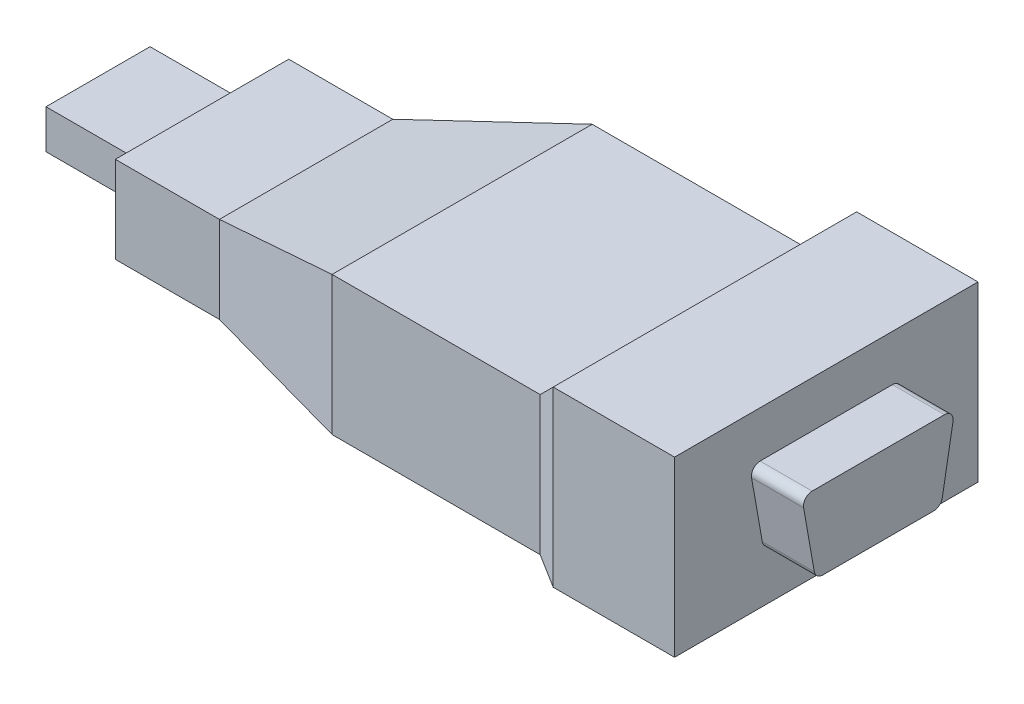
SolidWorks part; units mm, degrees
ref_plane "Top Plane" through (0, 0, 0) normal (0, 0, 1) x (1, 0, 0)
ref_plane "Right Plane" through (0, 0, 0) normal (0, 1, 0) x (1, 0, 0)
ref_plane "Front Plane" through (0, 0, 0) normal (1, 0, 0) x (0, 0, -1)
sketch "Sketch1" plane through (0, 0, 0) normal (1, 0, 0) x (0, 0, -1)
  line L1 (-17.5, -5) -> (17.5, -5)
  line L2 (-17.5, -5) -> (-17.5, 15)
  line L3 (-17.5, 15) -> (17.5, 15)
  line L4 (17.5, -5) -> (17.5, 15)
  line L5 (-17.5, -5) -> (17.5, 15) construction
  line L6 (-17.5, 15) -> (17.5, -5) construction
  point P0 (0, 5)
  dimension "D1" = 20
  dimension "D2" = 35
  dimension "D3" = 5
ref_plane "Plane1" through (-14, 0, 0) normal (1, 0, 0) x (0, 0, -1)
sketch "Sketch2" plane through (-14, 0, 0) normal (1, 0, 0) x (0, 0, -1)
  line L1 (-17.5, -5) -> (17.5, -5)
  line L2 (-17.5, -5) -> (-17.5, 15)
  line L3 (-17.5, 15) -> (17.5, 15)
  line L4 (17.5, -5) -> (17.5, 15)
  line L5 (-17.5, -5) -> (17.5, 15) construction
  line L6 (-17.5, 15) -> (17.5, -5) construction
  point P0 (0, 5)
  dimension "D1" = 35
  dimension "D2" = 20
  dimension "D3" = 5
ref_plane "Plane2" through (-18, 0, 0) normal (1, 0, 0) x (0, 0, -1)
sketch "Sketch3" plane through (-18, 0, 0) normal (1, 0, 0) x (0, 0, -1)
  line L1 (-15, -5) -> (15, -5)
  line L2 (-15, -5) -> (-15, 11)
  line L3 (-15, 11) -> (15, 11)
  line L4 (15, -5) -> (15, 11)
  line L5 (-15, -5) -> (15, 11) construction
  line L6 (-15, 11) -> (15, -5) construction
  point P0 (0, 3)
  point P6 (0, 3)
  dimension "D1" = 16
  dimension "D2" = 30
  dimension "D3" = 5
ref_plane "Plane3" through (-42, 0, 0) normal (1, 0, 0) x (0, 0, -1)
sketch "Sketch4" plane through (-42, 0, 0) normal (1, 0, 0) x (0, 0, -1)
  line L1 (-15, -5) -> (15, -5)
  line L2 (-15, -5) -> (-15, 11)
  line L3 (-15, 11) -> (15, 11)
  line L4 (15, -5) -> (15, 11)
  line L5 (-15, -5) -> (15, 11) construction
  line L6 (-15, 11) -> (15, -5) construction
  point P0 (0, 3)
  dimension "D1" = 16
  dimension "D2" = 30
  dimension "D3" = 5
ref_plane "Plane4" through (-60, 0, 0) normal (1, 0, 0) x (0, 0, -1)
ref_plane "Plane5" through (-72, 0, 0) normal (1, 0, 0) x (0, 0, -1)
sketch "Sketch5" plane through (-60, 0, 0) normal (1, 0, 0) x (0, 0, -1)
  line L1 (-10, 5) -> (10, 5)
  line L2 (-10, 5) -> (-10, -5)
  line L3 (-10, -5) -> (10, -5)
  line L4 (10, 5) -> (10, -5)
  line L5 (-10, 5) -> (10, -5) construction
  line L6 (-10, -5) -> (10, 5) construction
  point P0 (0, 0)
  dimension "D1" = 10
  dimension "D2" = 20
loft "Loft1" add profiles "Sketch1", "Sketch2" connector at (0, 15, 17.5) connector at (-14, 15, 17.5)
loft "Loft2" add profiles "Sketch2<3>", "Sketch3" connector at (-14, 15, -17.5) connector at (-18, 11, -15)
sketch "Sketch2<3>" plane through (-14, 0, 0) normal (1, 0, 0) x (0, 0, -1) same geometry as "Sketch2"
loft "Loft3" add profiles "Sketch3<3>", "Sketch4" connector at (-18, 11, 15) connector at (-42, 11, 15)
sketch "Sketch3<3>" plane through (-18, 0, 0) normal (1, 0, 0) x (0, 0, -1) same geometry as "Sketch3"
loft "Loft4" add profiles "Sketch4<3>", "Sketch5" connector at (-42, 11, -15) connector at (-60, 5, -10)
sketch "Sketch4<3>" plane through (-42, 0, 0) normal (1, 0, 0) x (0, 0, -1) same geometry as "Sketch4"
sketch "Sketch8" plane through (-72, 0, 0) normal (1, 0, 0) x (0, 0, -1)
  line L1 (10, -5) -> (-10, -5)
  line L2 (10, -5) -> (10, 5)
  line L3 (10, 5) -> (-10, 5)
  line L4 (-10, -5) -> (-10, 5)
loft "Loft5" add profiles "Sketch5<4>", "Sketch8" connector at (-60, 5, -10) connector at (-72, 5, -10)
sketch "Sketch5<4>" plane through (-60, 0, 0) normal (1, 0, 0) x (0, 0, -1) same geometry as "Sketch5"
sketch "Sketch6" plane through (-72, 0, 0) normal (-1, 0, 0) x (0, 0, 1)
  line L1 (-6, -2.25) -> (6, -2.25)
  line L2 (-6, -2.25) -> (-6, 2.25)
  line L3 (-6, 2.25) -> (6, 2.25)
  line L4 (6, -2.25) -> (6, 2.25)
  line L5 (-6, -2.25) -> (6, 2.25) construction
  line L6 (-6, 2.25) -> (6, -2.25) construction
  point P0 (0, 0)
  dimension "D1" = 12
  dimension "D2" = 4.5
extrude "Boss-Extrude1" add sketch "Sketch6" along normal blind 12
sketch "Sketch7" plane through (0, 0, 0) normal (1, 0, 0) x (0, 0, -1)
  line L0 (-7.6323, 9.6736) -> (7.6323, 9.6736)
  line L1 (8.6171, 8.5) -> (7.3829, 1.5)
  line L2 (6.398, 0.6736) -> (-6.398, 0.6736)
  line L3 (-7.3829, 1.5) -> (-8.6171, 8.5)
  line L4 (0, 0.6736) -> (0, 9.6736) construction
  line L5 (-8, 5) -> (8, 5) construction
  line L6 (0, 15) -> (0, -5) construction
  line L7 (17.5, 15) -> (-17.5, 15) construction
  line L8 (-17.5, -5) -> (17.5, -5) construction
  arc A0 (7.6323, 9.6736) -> (8.6171, 8.5) centre (7.6323, 8.6736) cw
  arc A1 (7.3829, 1.5) -> (6.398, 0.6736) centre (6.398, 1.6736) cw
  arc A2 (-6.398, 0.6736) -> (-7.3829, 1.5) centre (-6.398, 1.6736) cw
  arc A3 (-7.6323, 9.6736) -> (-8.6171, 8.5) centre (-7.6323, 8.6736) ccw
  point P23 (0, 5)
  dimension "D5" = 1
  dimension "D1" = 80
  dimension "D2" = 16
  dimension "D3" = 9
  dimension "D4" = 80
extrude "Boss-Extrude2" add sketch "Sketch7" along normal blind 6
sketch "Sketch9" plane through (0, 0, -15) normal (0, 0, -1) x (-1, 0, 0)
  line L0 (18, -5) -> (42, -5) construction
  line L1 (41, 0) -> (18, 0)
  line L2 (41, 0) -> (41, 6)
  line L3 (41, 6) -> (18, 6)
  line L4 (18, 0) -> (18, 6)
  line L5 (18, 11) -> (42, 11) construction
  line L6 (18, -5) -> (18, 11) construction
  line L7 (42, -5) -> (42, 11) construction
  dimension "D1" = 5
  dimension "D2" = 5
  dimension "D3" = 1
extrude "Cut-Extrude1" cut sketch "Sketch9" against normal blind 5
